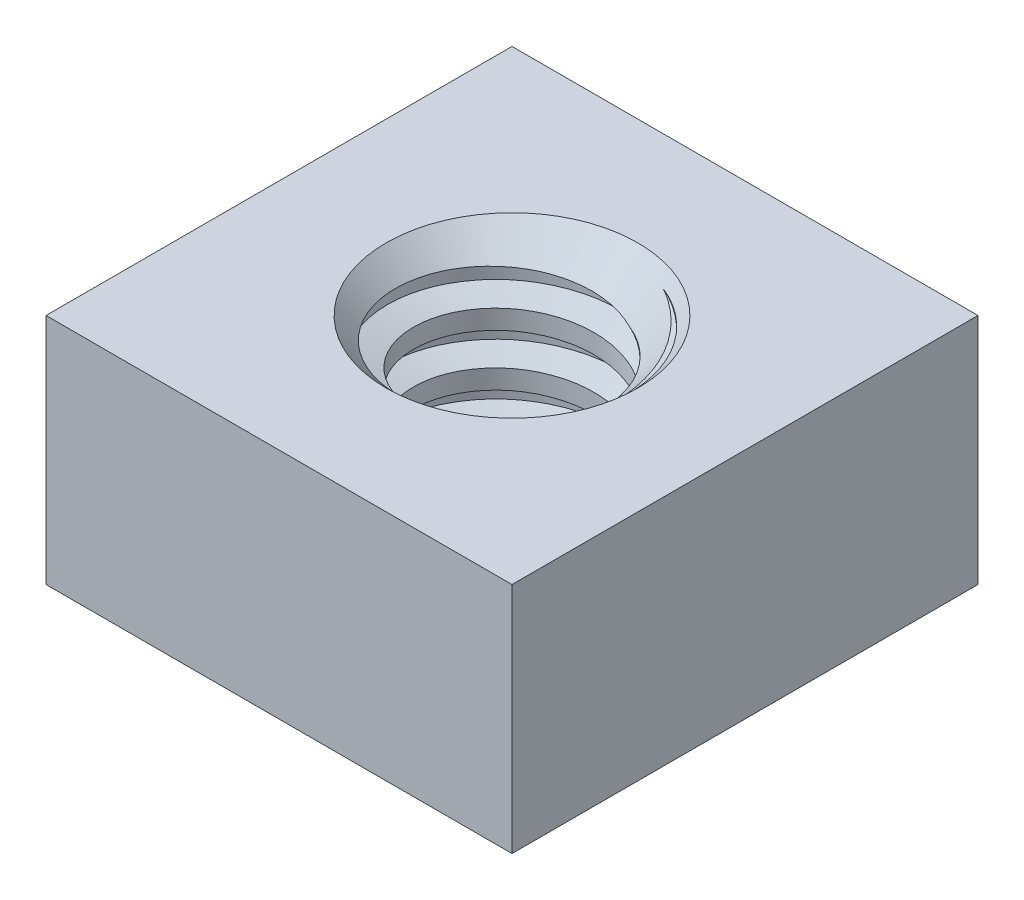
SolidWorks part; units mm, degrees
ref_plane "Front" through (0, 0, 0) normal (0, 0, 1) x (1, 0, 0)
ref_plane "Top" through (0, 0, 0) normal (0, 1, 0) x (1, 0, 0)
ref_plane "Right" through (0, 0, 0) normal (1, 0, 0) x (0, 0, -1)
sketch "Sketch1" plane through (0, 0, 0) normal (0, 1, 0) x (1, 0, 0)
  line L1 (-9.525, 9.525) -> (9.525, 9.525)
  line L2 (-9.525, 9.525) -> (-9.525, -9.525)
  line L3 (-9.525, -9.525) -> (9.525, -9.525)
  line L4 (9.525, 9.525) -> (9.525, -9.525)
  line L5 (-9.525, 9.525) -> (9.525, -9.525) construction
  line L6 (-9.525, -9.525) -> (9.525, 9.525) construction
  circle A0 centre (0, 0) radius 4.7625
  dimension "Width" = 19.05
  dimension "ThreadDia" = 9.525
extrude "Boss-Extrude1" add sketch "Sketch1" along normal mid plane 9.525
sketch "Sketch2" plane through (0, 4.7625, 0) normal (0, 1, 0) x (1, 0, 0)
  circle A0 centre (0, 0) radius 4.7625 construction
  circle A1 centre (0, 0) radius 4.7625
curve "Helix/Spiral1" pitch 2.1167 height 11.6417 radius 4.7625 centre (0, 4.7625, 0) axis (0, -1, 0) start towards (1, 0, 0) parameters "Pitch"=2.1167
sketch "Sketch3" plane through (0, 0, 0) normal (0, 0, 1) x (1, 0, 0)
  line L0 (4.7625, 4.7625) -> (3.7042, 5.0362)
  line L1 (-9.525, 4.7625) -> (9.525, 4.7625) construction
  line L2 (3.7042, 5.0362) -> (3.7042, 5.8208)
  line L3 (3.7042, 5.8208) -> (4.7625, 6.0945)
  line L4 (4.7625, 6.0945) -> (4.7625, 4.7625)
  line L5 (4.2334, 4.8993) -> (4.2334, 5.9577) construction
  line L6 (4.2334, 5.4285) -> (3.7042, 5.4285) construction
  spline S0 degree 3 poles (4.7625, 4.7625) (4.7625, 4.7187) (4.5145, 4.6301) (3.4553, 4.498) (1.87, 4.3656) (0, 4.2333) (-1.87, 4.101) (-3.4553, 3.9688) (-4.5145, 3.8365) (-4.8865, 3.7042) (-4.5145, 3.5719) (-3.4553, 3.4396) (-1.87, 3.3073) (0, 3.175) (1.87, 3.0427) (3.4553, 2.9104) (4.5145, 2.7781) (4.8865, 2.6458) (4.5145, 2.5135) (3.4553, 2.3813) (1.87, 2.249) (0, 2.1167) (-1.87, 1.9844) (-3.4553, 1.8521) (-4.5145, 1.7198) (-4.8865, 1.5875) (-4.5145, 1.4552) (-3.4553, 1.3229) (-1.87, 1.1906) (0, 1.0583) (1.87, 0.926) (3.4553, 0.7937) (4.5145, 0.6615) (4.8865, 0.5292) (4.5145, 0.3969) (3.4553, 0.2646) (1.87, 0.1323) (0, 0) (-1.87, -0.1323) (-3.4553, -0.2646) (-4.5145, -0.3969) (-4.8865, -0.5292) (-4.5145, -0.6615) (-3.4553, -0.7938) (-1.87, -0.926) (0, -1.0583) (1.87, -1.1906) (3.4553, -1.3229) (4.5145, -1.4552) (4.8865, -1.5875) (4.5145, -1.7198) (3.4553, -1.8521) (1.87, -1.9844) (0, -2.1167) (-1.87, -2.249) (-3.4553, -2.3813) (-4.5145, -2.5135) (-4.8865, -2.6458) (-4.5145, -2.7781) (-3.4553, -2.9104) (-1.87, -3.0427) (0, -3.175) (1.87, -3.3073) (3.4553, -3.4396) (4.5145, -3.5719) (4.8865, -3.7042) (4.5145, -3.8365) (3.4553, -3.9688) (1.87, -4.101) (0, -4.2333) (-1.87, -4.3656) (-3.4553, -4.4979) (-4.5145, -4.6302) (-4.8865, -4.7625) (-4.5145, -4.8948) (-3.4553, -5.0271) (-1.87, -5.1594) (0, -5.2917) (1.87, -5.424) (3.4553, -5.5563) (4.5145, -5.6885) (4.8865, -5.8208) (4.5145, -5.9531) (3.4553, -6.0854) (1.87, -6.2177) (0, -6.35) (-1.87, -6.4823) (-3.4553, -6.6146) (-4.5145, -6.7467) (-4.7625, -6.8354) (-4.7625, -6.8792) knots 0 0 0 0 0.011364 0.022727 0.034091 0.045455 0.056818 0.068182 0.079545 0.090909 0.102273 0.113636 0.125 0.136364 0.147727 0.159091 0.170455 0.181818 0.193182 0.204545 0.215909 0.227273 0.238636 0.25 0.261364 0.272727 0.284091 0.295455 0.306818 0.318182 0.329545 0.340909 0.352273 0.363636 0.375 0.386364 0.397727 0.409091 0.420455 0.431818 0.443182 0.454545 0.465909 0.477273 0.488636 0.5 0.511364 0.522727 0.534091 0.545455 0.556818 0.568182 0.579545 0.590909 0.602273 0.613636 0.625 0.636364 0.647727 0.659091 0.670455 0.681818 0.693182 0.704545 0.715909 0.727273 0.738636 0.75 0.761364 0.772727 0.784091 0.795455 0.806818 0.818182 0.829545 0.840909 0.852273 0.863636 0.875 0.886364 0.897727 0.909091 0.920455 0.931818 0.943182 0.954545 0.965909 0.977273 0.988636 1 1 1 1 construction
  dimension "D1" = 29
  dimension "D2" = 0.7846
  dimension "D3" = 1.0583
sketch "Sketch4" plane through (0, 4.7625, 0) normal (0, 1, 0) x (1, 0, 0)
  circle A0 centre (0, 0) radius 5.1435
  circle A1 centre (0, 0) radius 4.7625 construction
  dimension "D1" = 0.381
sketch "Sketch5" plane through (0, -4.7625, 0) normal (0, -1, 0) x (1, 0, 0)
  circle A1 centre (0, 0) radius 5.1435
  circle A2 centre (0, 0) radius 5.1435
  dimension "D1" = 0
sweep "Sweep1" add profiles "Sketch3" path "Helix/Spiral1"
extrude "Cut-Extrude1" cut sketch "Sketch4" along normal through all
extrude "Cut-Extrude2" cut sketch "Sketch5" along normal through all
extrude "Cut-Extrude3" cut sketch "Sketch4<2>" against normal through all draft 45
sketch "Sketch4<2>" plane through (0, 4.7625, 0) normal (0, 1, 0) x (1, 0, 0) same geometry as "Sketch4"
extrude "Cut-Extrude4" cut sketch "Sketch5<2>" against normal through all draft 45
sketch "Sketch5<2>" plane through (0, -4.7625, 0) normal (0, -1, 0) x (1, 0, 0) same geometry as "Sketch5"
equation "\"D3@Helix/Spiral1\" = \"Height@Boss-Extrude1\"+\"Pitch@Helix/Spiral1\""
equation "\"D2@Sketch3\" = \"Pitch@Helix/Spiral1\"*.3707"
equation "\"D3@Sketch3\" = \"Pitch@Helix/Spiral1\"*.5"
